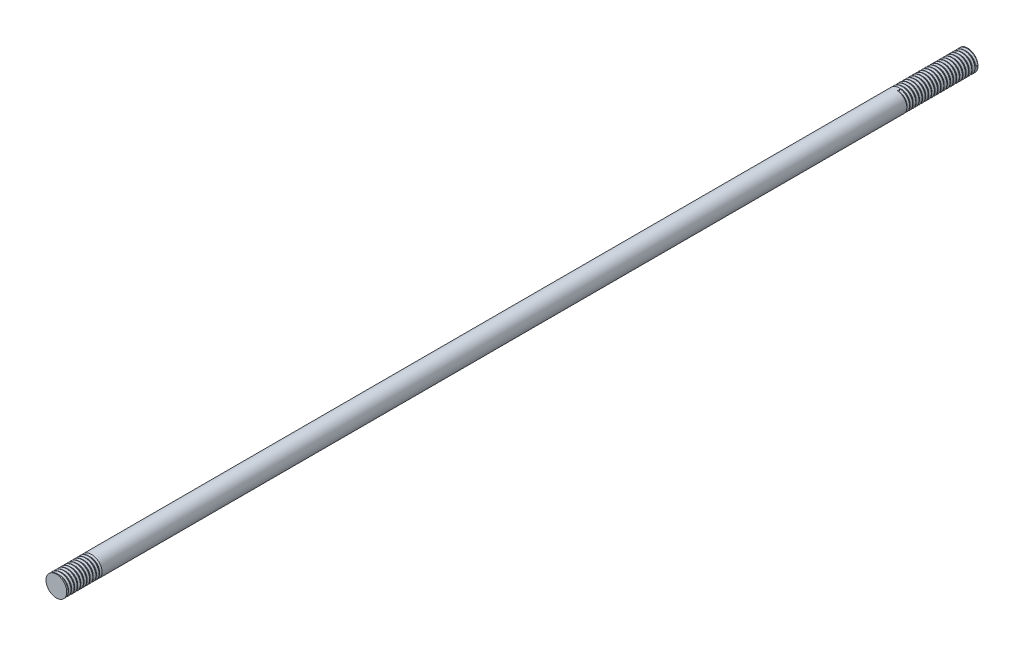
SolidWorks part; units mm, degrees
ref_plane "Alzado" through (0, 0, 0) normal (0, 0, 1) x (1, 0, 0)
ref_plane "Planta" through (0, 0, 0) normal (0, 1, 0) x (1, 0, 0)
ref_plane "Vista lateral" through (0, 0, 0) normal (1, 0, 0) x (0, 0, -1)
sketch "Croquis1" plane through (0, 0, 0) normal (0, 0, 1) x (1, 0, 0)
  circle A0 centre (0, 0) radius 1.5
  dimension "D1" = 3
extrude "Saliente-Extruir1" add sketch "Croquis1" along normal blind 131.84
cosmetic thread "Rosca cosmética1" parameters "D2"=2.439
thread "Rosca1" pitch 0.45 method cut profile "Perfil de rosca1" start angle 0, offset 0, length 5, pitch 0.45, diameter 3
ref_plane "Plano1" through (-1.5, 0, 131.84) normal (0, -1, 0) x (-1, 0, 0)
sketch "Perfil de rosca1" plane through (-1.5, 0, 131.84) normal (0, -1, 0) x (-1, 0, 0)
  line L0 (0, 0) -> (0, 0.45) construction
  line L11 (0, 0) -> (0, 0.3937)
  line L12 (0, 0.3937) -> (-0.2436, 0.2531)
  line L13 (-0.2436, 0.2531) -> (-0.2436, 0.1406)
  line L15 (-0.2436, 0.1406) -> (0, 0)
  line L17 (-0.2436, 0.1969) -> (0, 0.1969) construction
  point P2 (0, 0)
  dimension "Pitch" = 0.45
  dimension "Profile_Angle" = 60
  dimension "Profile_Land" = 0.1125
  dimension "Profile_Height" = 0.2436
thread "Rosca2" pitch 0.45 method cut profile "Perfil de rosca2" start angle 0, offset 0, length 10, pitch 0.45, diameter 3
ref_plane "Plano2" through (1.5, 0, 0) normal (0, -1, 0) x (1, 0, 0)
sketch "Perfil de rosca2" plane through (1.5, 0, 0) normal (0, -1, 0) x (1, 0, 0)
  line L0 (0, 0) -> (0, 0.45) construction
  line L11 (0, 0) -> (0, 0.3937)
  line L12 (0, 0.3937) -> (-0.2436, 0.2531)
  line L13 (-0.2436, 0.2531) -> (-0.2436, 0.1406)
  line L15 (-0.2436, 0.1406) -> (0, 0)
  line L17 (-0.2436, 0.1969) -> (0, 0.1969) construction
  point P2 (0, 0)
  dimension "Pitch" = 0.45
  dimension "Profile_Angle" = 60
  dimension "Profile_Land" = 0.1125
  dimension "Profile_Height" = 0.2436
equation "\"D1@Saliente-Extruir1\"=131.84"
